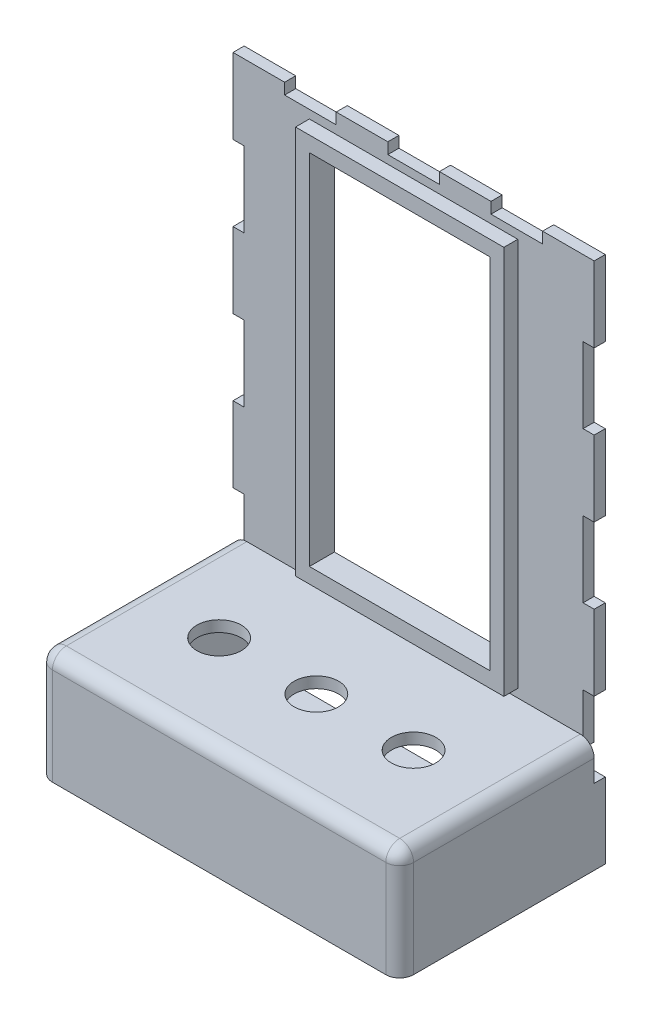
SolidWorks part; units mm, degrees
ref_plane "Front Plane" through (0, 0, 0) normal (0, 0, 1) x (1, 0, 0)
ref_plane "Top Plane" through (0, 0, 0) normal (0, 1, 0) x (1, 0, 0)
ref_plane "Right Plane" through (0, 0, 0) normal (1, 0, 0) x (0, 0, -1)
sketch "Buitenafmeting Rechthoek" plane through (0, 0, 0) normal (0, 0, 1) x (1, 0, 0)
  line L1 (0, 0) -> (130, 0)
  line L2 (0, 0) -> (0, 190)
  line L3 (0, 190) -> (130, 190)
  line L4 (130, 0) -> (130, 190)
  dimension "D1" = 130
  dimension "D2" = 190
extrude "Plaat" add sketch "Buitenafmeting Rechthoek" against normal blind 4
sketch "Tand Hor" plane through (0, 0, 0) normal (0, 0, 1) x (1, 0, 0)
  line L1 (130, 190) -> (0, 190) construction
  line L2 (18.5714, 190) -> (37.1429, 190)
  line L3 (18.5714, 190) -> (18.5714, 186)
  line L4 (18.5714, 186) -> (37.1429, 186)
  line L6 (37.1429, 190) -> (37.1429, 186)
  dimension "D1" = 4
  dimension "D2" = 18.5714
  dimension "D3" = 18.5714
extrude "Tand Boven" cut sketch "Tand Hor" against normal through all
pattern_linear "Tanden Patroon Boven" count 3 spacing 37.1429 along (1, 0, 0) of "Tand Boven"
sketch "Tand Ver" plane through (0, 0, 0) normal (0, 0, 1) x (1, 0, 0)
  line L0 (0, 190) -> (0, 0) construction
  line L1 (0, 162.8571) -> (4, 162.8571)
  line L2 (0, 162.8571) -> (0, 135.7143)
  line L3 (0, 135.7143) -> (4, 135.7143)
  line L4 (4, 162.8571) -> (4, 135.7143)
  dimension "D1" = 4
  dimension "D2" = 27.1429
  dimension "D3" = 162.8571
extrude "Tand Links" cut sketch "Tand Ver" against normal through all
pattern_linear "Tanden Patroon Links" count 3 spacing 54.2857 along (0, -1, 0) of "Tand Links"
sketch "Tand O" plane through (0, 0, 0) normal (0, 0, 1) x (1, 0, 0)
  line L0 (0, 0) -> (130, 0) construction
  line L1 (18.5714, 0) -> (37.1429, 0)
  line L2 (18.5714, 0) -> (18.5714, 4)
  line L3 (18.5714, 4) -> (37.1429, 4)
  line L4 (37.1429, 0) -> (37.1429, 4)
  dimension "D1" = 4
  dimension "D2" = 18.5714
  dimension "D3" = 18.5714
extrude "Tand Onder" cut sketch "Tand O" against normal through all
pattern_linear "Tanden Patroon Onder" count 3 spacing 37.1429 along (1, 0, 0) of "Tand Onder"
sketch "Tand R" plane through (0, 0, 0) normal (0, 0, 1) x (1, 0, 0)
  line L0 (130, 0) -> (130, 190) construction
  line L1 (130, 162.8571) -> (126, 162.8571)
  line L2 (130, 162.8571) -> (130, 135.7143)
  line L3 (130, 135.7143) -> (126, 135.7143)
  line L4 (126, 162.8571) -> (126, 135.7143)
  dimension "D1" = 4
  dimension "D2" = 27.1429
  dimension "D3" = 162.8571
extrude "Tand Rechts" cut sketch "Tand R" against normal through all
pattern_linear "Tanden Patroon Rechts" count 3 spacing 54.2857 along (0, -1, 0) of "Tand Rechts"
sketch "Sketch1" plane through (0, 0, 0) normal (0, 0, 1) x (1, 0, 0)
  line L0 (130, 54.2857) -> (130, 81.4286) construction
  line L1 (0, 0) -> (130, 0)
  line L2 (0, 0) -> (0, 40)
  line L3 (0, 40) -> (130, 40)
  line L4 (130, 0) -> (130, 40)
  dimension "D1" = 40
extrude "Boss-Extrude1" add sketch "Sketch1" along normal blind 70
fillet "Fillet1" radius 5 5 edges at (0, 20, 70) (130, 20, 70) (0, 40, 35) (65, 40, 70) (130, 40, 35)
sketch "Sketch2" plane through (0, 0, -4) normal (0, 0, -1) x (-1, 0, 0)
  line L1 (-4, 27.1429) -> (-4, 54.2857) construction
  line L2 (-92.8571, 4) -> (-4, 4)
  line L4 (-92.8571, 36) -> (-4, 36)
  line L5 (-4, 4) -> (-4, 36)
  line L6 (-126, 39.899) -> (-126, 27.1429) construction
  line L7 (-92.8571, 4) -> (-126, 4)
  line L9 (-92.8571, 36) -> (-126, 36)
  line L10 (-126, 4) -> (-126, 36)
  dimension "D1" = 32
  dimension "D2" = 32
extrude "Cut-Extrude1" cut sketch "Sketch2" against normal blind 70
sketch "Sketch4" plane through (0, 40, 0) normal (0, 1, 0) x (1, 0, 0)
  line L0 (5, 0) -> (5, -65) construction
  line L1 (125, -65) -> (125, 0) construction
  line L2 (5, -65) -> (125, -65) construction
  circle A0 centre (65, -35) radius 8
  circle A1 centre (100, -35) radius 8
  circle A2 centre (30, -35) radius 8
  dimension "D1" = 16
  dimension "D2" = 16
  dimension "D3" = 16
  dimension "D4" = 60
  dimension "D5" = 60
  dimension "D6" = 30
  dimension "D7" = 35
  dimension "D8" = 35
  dimension "D9" = 35
extrude "Cut-Extrude2" cut sketch "Sketch4" against normal blind 27
sketch "Sketch5" plane through (0, 0, 0) normal (0, 0, 1) x (1, 0, 0)
  line L0 (0, 135.7143) -> (0, 108.5714) construction
  line L1 (27.5, 183) -> (102.5, 183)
  line L2 (27.5, 183) -> (27.5, 43)
  line L3 (27.5, 43) -> (102.5, 43)
  line L4 (102.5, 183) -> (102.5, 43)
  line L5 (130, 108.5714) -> (130, 135.7143) construction
  line L6 (55.7143, 186) -> (74.2857, 186) construction
  line L7 (125, 40) -> (5, 40) construction
  dimension "D1" = 140
  dimension "D2" = 75
  dimension "D3" = 27.5
  dimension "D4" = 27.5
  dimension "D5" = 3
  dimension "D6" = 3
extrude "Boss-Extrude2" add sketch "Sketch5" along normal blind 5
sketch "Sketch6" plane through (0, 0, 5) normal (0, 0, 1) x (1, 0, 0)
  line L0 (102.5, 183) -> (27.5, 183) construction
  line L1 (32.5, 177.5) -> (97.5, 177.5)
  line L2 (32.5, 177.5) -> (32.5, 48.5)
  line L3 (32.5, 48.5) -> (97.5, 48.5)
  line L4 (97.5, 177.5) -> (97.5, 48.5)
  line L5 (27.5, 43) -> (102.5, 43) construction
  line L6 (27.5, 183) -> (27.5, 43) construction
  line L8 (102.5, 43) -> (102.5, 183) construction
  dimension "D1" = 129
  dimension "D2" = 65
  dimension "D3" = 5.5
  dimension "D4" = 5.5
  dimension "D5" = 5
  dimension "D6" = 5
extrude "Cut-Extrude3" cut sketch "Sketch6" against normal blind 30
equation "\"D1@Buitenafmeting Rechthoek\"= \"Lengte\""
equation "\"D2@Buitenafmeting Rechthoek\" = \"Hoogte\""
equation "\"D1@Plaat\" = \"Dikte\""
equation "\"D3@Tanden Patroon Boven\" = \"LengteHorTand\" * 2"
equation "\"D1@Tanden Patroon Boven\" = \"nPatroonHor\""
equation "\"LengteHorTand\"= \"Lengte\" / \"nHor\"'Spatie tussen verschillende tanden in de lengte"
equation "\"nPatroonHor\"= ( \"nHor\" + 1 ) / 2 - \"GrensHor\"'Aantal kopies van tanden in de lengte"
equation "\"D1@Tand Hor\" = \"Dikte\""
equation "\"D2@Tand Hor\" = \"LengteHorTand\""
equation "\"D1@Tand Ver\" = \"Dikte\""
equation "\"LengteVertTand\"= \"Hoogte\" / \"nVert\"'Spatie tussen verschillende tanden in de hoogte"
equation "\"nPatroonVert\"= ( \"nVert\" + 1 ) / 2 - \"GrensVert\"'Aantal kopies van tanden in de hoogte"
equation "\"D2@Tand Ver\"=\"LengteVertTand\""
equation "\"D3@Tanden Patroon Links\"=\"LengteVertTand\"*2"
equation "\"D3@Tanden Patroon Rechts\"=\"LengteVertTand\"*2"
equation "\"D1@Tanden Patroon Rechts\"=\"nPatroonVert\""
equation "\"D3@Tanden Patroon Onder\"=\"LengteHorTand\"*2"
equation "\"D1@Tanden Patroon Onder\"=\"nPatroonHor\""
equation "\"D1@Tanden Patroon Links\"=\"nPatroonVert\""
equation "\"D3@Tand Ver\"=\"Hoogte\"-\"GrensVert\"*\"LengteVertTand\""
equation "\"D2@Tand R\" = \"LengteVertTand\""
equation "\"D3@Tand R\" = \"Hoogte\" - \"GrensVert\" * \"LengteVertTand\""
equation "\"D2@Tand O\"=\"LengteHorTand\""
equation "\"D3@Tand Hor\"=\"GrensHor\"*\"LengteHorTand\""
equation "\"D3@Tand O\"=\"GrensHor\"*\"LengteHorTand\""
equation "\"Tand Boven\"= IIF ( \"plaatsTandenBoven\" , \"unsuppressed\" , \"suppressed\" )"
equation "\"Tanden Patroon Boven\"= IIF ( \"plaatsTandenBoven\" , \"unsuppressed\" , \"suppressed\" )"
equation "\"Tand Links\"= IIF ( \"plaatsTandenLinks\" , \"unsuppressed\" , \"suppressed\" )"
equation "\"Tanden Patroon Links\"= IIF ( \"plaatsTandenLinks\" , \"unsuppressed\" , \"suppressed\" )"
equation "\"Tand Onder\"= IIF ( \"plaatsTandenOnder\" , \"unsuppressed\" , \"suppressed\" )"
equation "\"Tanden Patroon Onder\"= IIF ( \"plaatsTandenOnder\" , \"unsuppressed\" , \"suppressed\" )"
equation "\"Tand Rechts\"= IIF ( \"plaatsTandenRechts\" , \"unsuppressed\" , \"suppressed\" )"
equation "\"Tanden Patroon Rechts\"= IIF ( \"plaatsTandenRechts\" , \"unsuppressed\" , \"suppressed\" )"
equation "\"D1@Tand O\"=\"Dikte\""
equation "\"D1@Tand R\"=\"Dikte\""
